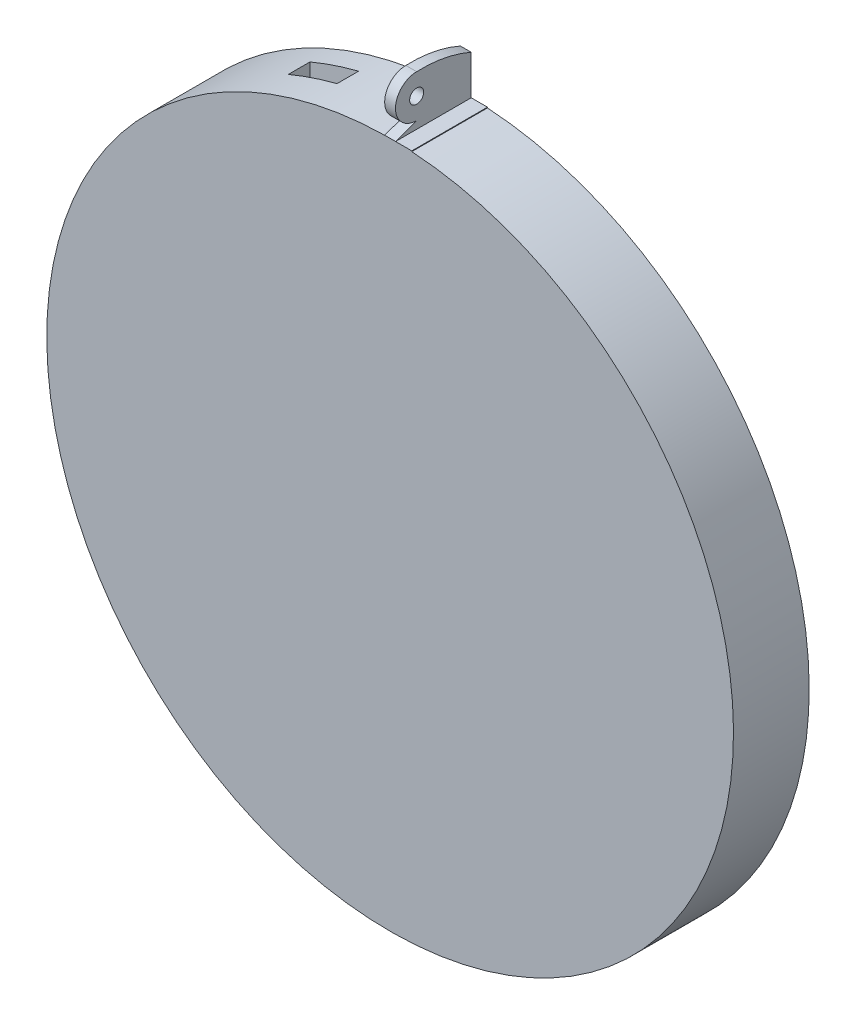
SolidWorks part; units mm, degrees
ref_plane "Front Plane" through (0, 0, 0) normal (0, 0, 1) x (1, 0, 0)
ref_plane "Top Plane" through (0, 0, 0) normal (0, 1, 0) x (1, 0, 0)
ref_plane "Right Plane" through (0, 0, 0) normal (1, 0, 0) x (0, 0, -1)
sketch "Sketch1" plane through (0, 0, 0) normal (0, 0, 1) x (1, 0, 0)
  circle A0 centre (0, 0) radius 63.5
  dimension "D1" = 127
extrude "Boss-Extrude2" add sketch "Sketch1" along normal blind 23
shell "Shell4" thickness 3 removed face at (63.5, 0, 0)
sketch "Sketch4" plane through (0, 0, 20) normal (0, 0, -1) x (-1, 0, 0)
  circle A0 centre (0, 0) radius 56.097
extrude "Cut-Extrude1" cut sketch "Sketch4" against normal blind 22
sketch "Sketch8" plane through (0, 0, 0) normal (1, 0, 0) x (0, 0, -1)
  line L0 (-23, 63.5) -> (0, 63.5)
  arc A0 (-19.0928, 72.7285) -> (-19.0928, 64.8949) centre (-19.0928, 68.8117) ccw
  circle A1 centre (-19.0928, 68.8117) radius 1.3
  arc A2 (-19.0928, 72.7285) -> (0, 63.5) centre (-18.1616, 50.2902) cw
  arc A3 (-19.0928, 64.8949) -> (-23, 63.5) centre (37.5589, -99.9637) ccw
  dimension "D1" = 2.6
extrude "Boss-Extrude6" add sketch "Sketch8" along normal blind 1 and the other way blind 1 separate body
sketch "Sketch9" plane through (0, 63.5, 0) normal (0, -1, 0) x (1, 0, 0)
  line L1 (-1, 23) -> (4, 23)
  line L2 (-1, 23) -> (-1, 0)
  line L3 (-1, 0) -> (4, 0)
  line L4 (4, 23) -> (4, 0)
extrude "Boss-Extrude7" add sketch "Sketch9" along normal up to surface (0.1261 mm away) up to face at (63.5, 0, 23)
sketch "Sketch11" plane through (0, 0, 0) normal (0, 0, -1) x (-1, 0, 0)
  circle A0 centre (0, 0) radius 63.5
extrude "Cut-Extrude2" cut sketch "Sketch11" against normal blind 9
sketch "Sketch12" plane through (0, 0, 9) normal (0, 0, -1) x (-1, 0, 0)
  line L1 (-8.4028, 62.9416) -> (11.0774, 62.9416)
  line L2 (-8.4028, 62.9416) -> (-8.4028, 75.1639)
  line L3 (-8.4028, 75.1639) -> (11.0774, 75.1639)
  line L4 (11.0774, 62.9416) -> (11.0774, 75.1639)
  arc A0 (-4, 63.3739) -> (1, 63.4921) centre (0, 0) ccw construction
extrude "Cut-Extrude3" cut sketch "Sketch12" along normal blind 13
sketch "Sketch13" plane through (0, 0, 23) normal (0, 0, 1) x (1, 0, 0)
  circle A0 centre (0, 0) radius 63.5
extrude "Boss-Extrude8" add sketch "Sketch13" against normal blind 2
sketch "Sketch15" plane through (0, 0, 0) normal (0, 1, 0) x (1, 0, 0)
  line L1 (-24.6344, -13.1992) -> (-15.6344, -13.1992)
  line L2 (-24.6344, -13.1992) -> (-24.6344, -17.1992)
  line L3 (-24.6344, -17.1992) -> (-15.6344, -17.1992)
  line L4 (-15.6344, -13.1992) -> (-15.6344, -17.1992)
  dimension "D1" = 9
  dimension "D2" = 4
extrude "Cut-Extrude4" cut sketch "Sketch15" along normal blind 89
sketch "Sketch16" plane through (0, 0, 21) normal (0, 0, -1) x (-1, 0, 0)
  line L0 (0, 0) -> (10, 0) construction
  circle A0 centre (10, -17.5) radius 1.5
  circle A1 centre (10, 17.5) radius 1.5
  point P6 (10, 0)
  dimension "D3" = 3
  dimension "D4" = 3
  dimension "D1" = 10
extrude "Boss-Extrude9" add sketch "Sketch16" along normal blind 10
